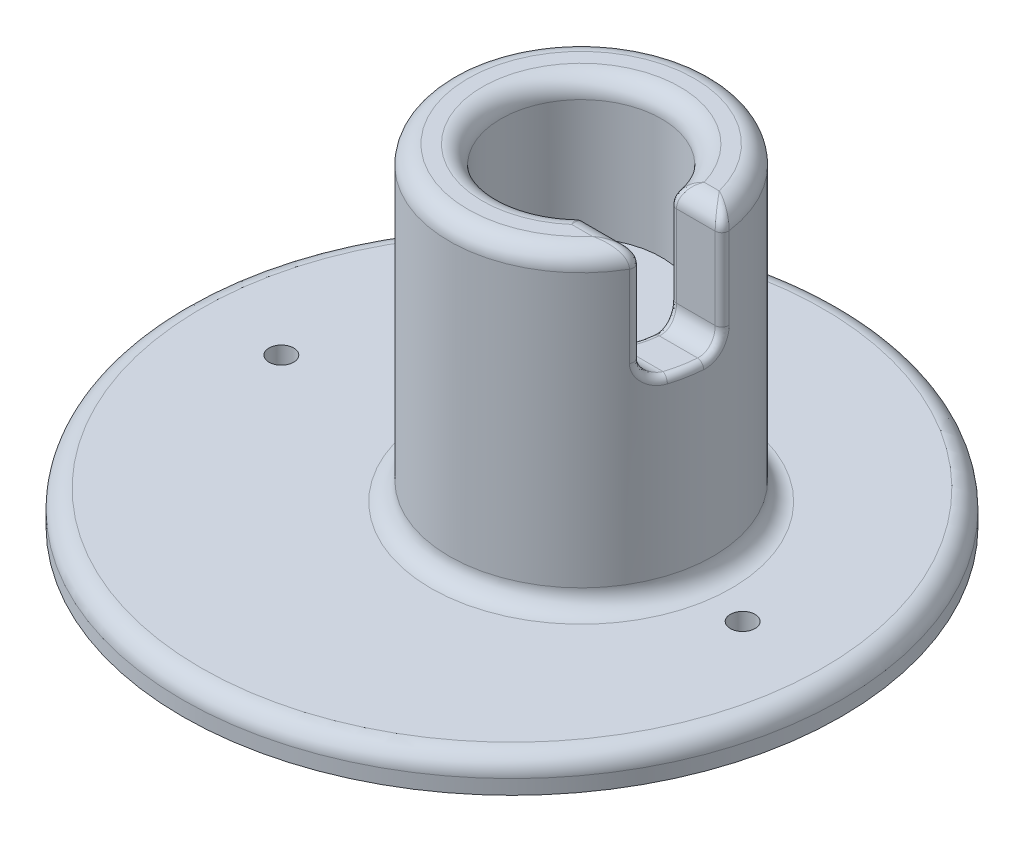
SolidWorks part; units mm, degrees
other "Markup1"
sketch "Sketch7" plane through (-63.5, 66.3699, -63.5) normal (-0.0026, 0.9999, -0.0156) x (0.9982, 0.0036, 0.0604)
material "ABS"
ref_plane "Front Plane" through (0, 0, 0) normal (0, 0, 1) x (1, 0, 0)
ref_plane "Top Plane" through (0, 0, 0) normal (0, 1, 0) x (1, 0, 0)
ref_plane "Right Plane" through (0, 0, 0) normal (1, 0, 0) x (0, 0, -1)
sketch "Sketch1" plane through (0, 0, 0) normal (0, 1, 0) x (1, 0, 0)
  circle A0 centre (0, 0) radius 7.62
  circle A1 centre (0, 0) radius 63.5
  dimension "D1" = 127
  dimension "D2" = 15.24
extrude "Boss-Extrude1" add sketch "Sketch1" along normal blind 6.35
sketch "Sketch2" plane through (0, 6.35, 0) normal (0, 1, 0) x (1, 0, 0)
  line L0 (9, 11.3527) -> (9, -3.5148) construction
  line L1 (8.89, 4.445) -> (9, 4.445) construction
  circle A0 centre (8.89, 4.445) radius 25.4
  circle A3 centre (8.89, 4.445) radius 15.494
  dimension "D1" = 50.8
  dimension "D2" = 4.445
  dimension "D3" = 30.988
  dimension "D4" = 9
extrude "Boss-Extrude2" add sketch "Sketch2" along normal blind 59.69
sketch "Sketch3" plane through (0, 66.04, 0) normal (0, 1, 0) x (1, 0, 0)
  line L8 (43.18, 6.35) -> (43.18, -6.35)
  line L9 (-1.27, 6.35) -> (43.18, 6.35)
  line L13 (-1.27, 6.35) -> (-1.27, -6.35)
  line L14 (-1.27, -6.35) -> (43.18, -6.35)
  circle A0 centre (0, 0) radius 7.62 construction
  dimension "D5" = 6.35
  dimension "D1" = 1.27
  dimension "D2" = 12.7
  dimension "D3" = 44.45
extrude "Cut-Extrude1" cut sketch "Sketch3" against normal blind 22.86
sketch "Sketch4" plane through (0, 6.35, 0) normal (0, 1, 0) x (1, 0, 0)
  circle A0 centre (44.45, 0) radius 2.3812
  circle A1 centre (-44.45, 0) radius 2.3812
  dimension "D1" = 4.7625
  dimension "D2" = 4.7625
  dimension "D3" = 44.45
  dimension "D4" = 44.45
extrude "Cut-Extrude2" cut sketch "Sketch4" against normal through all
fillet "Fillet1" radius 3.556 8 edges at (-16.0907, 66.04, -9.041) (29.2425, 66.04, -6.35) (-5.7989, 66.04, -9.3744) (25.9432, 66.04, 6.35) (25.9432, 43.18, 6.35) (29.2425, 43.18, -6.35) (8.89, 6.35, 20.955) (0, 6.35, 63.5)
fillet "Fillet2" radius 1.27 1 edges at (22.7483, 6.35, -11.3741)
fillet "Fillet3" radius 1.27 14 edges at (20.4615, 44.9324, 5.8587) (20.2892, 64.5782, 7.032) (30.8341, 64.5341, 7.0004) (24.7056, 64.309, -6.8541) (24.3749, 43.9279, -4.9757) (33.7516, 64.1773, -6.779) (20.0045, 54.61, 6.35) (31.8819, 54.61, 6.35) (24.2664, 54.61, -6.35) (34.2185, 54.61, -6.35) (23.7082, 43.18, 0.0812) (32.4276, 44.0307, 5.1019) (33.893, 43.18, 0.028) (34.2649, 44.5173, -5.573)
sketch "Sketch5" plane through (0, 6.35, 0) normal (0, 1, 0) x (1, 0, 0)
  circle A0 centre (8.89, 4.445) radius 15.494
extrude "Boss-Extrude3" add sketch "Sketch5" along normal blind 33.02
sketch "Sketch6" plane through (0, 0, 0) normal (0, -1, 0) x (1, 0, 0)
  circle A0 centre (0, 0) radius 7.62
extrude "Cut-Extrude3" cut sketch "Sketch6" against normal blind 12.7
